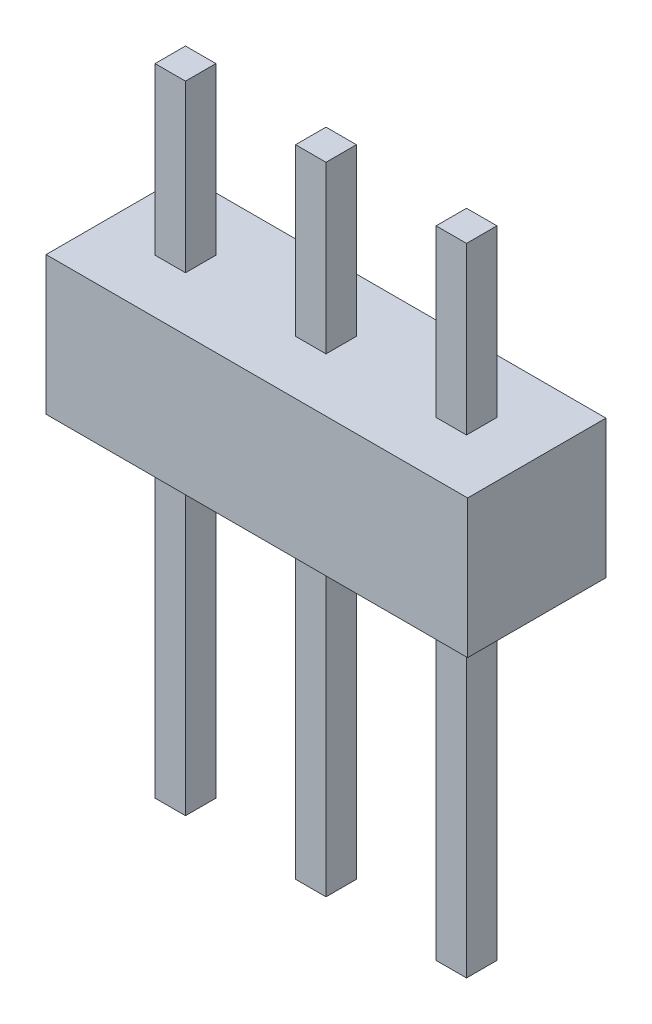
SolidWorks part; units mm, degrees
ref_plane "Front Plane" through (0, 0, 0) normal (0, 0, 1) x (1, 0, 0)
ref_plane "Top Plane" through (0, 0, 0) normal (0, 1, 0) x (1, 0, 0)
ref_plane "Right Plane" through (0, 0, 0) normal (1, 0, 0) x (0, 0, -1)
sketch "Sketch1" plane through (0, 0, 0) normal (0, 0, 1) x (1, 0, 0)
  line L1 (0, 0) -> (7.62, 0)
  line L2 (0, 0) -> (0, 2.5)
  line L3 (0, 2.5) -> (7.62, 2.5)
  line L4 (7.62, 0) -> (7.62, 2.5)
  dimension "D1" = 2.5
  dimension "D2" = 7.62
extrude "Boss-Extrude1" add sketch "Sketch1" along normal mid plane 2.5
sketch "Sketch2" plane through (0, 0, 0) normal (0, -1, 0) x (1, 0, 0)
  line L0 (0, 0) -> (7.62, 0) construction
  line L1 (7.62, 1.25) -> (7.62, -1.25) construction
  line L2 (3.535, -0.275) -> (4.085, -0.275)
  line L3 (0.995, -0.275) -> (1.545, -0.275)
  line L4 (0.995, -0.275) -> (0.995, 0.275)
  line L5 (0.995, 0.275) -> (1.545, 0.275)
  line L6 (1.545, -0.275) -> (1.545, 0.275)
  line L7 (0.995, -0.275) -> (1.545, 0.275) construction
  line L8 (0.995, 0.275) -> (1.545, -0.275) construction
  line L9 (3.535, -0.275) -> (3.535, 0.275)
  line L10 (3.535, 0.275) -> (4.085, 0.275)
  line L11 (4.085, -0.275) -> (4.085, 0.275)
  line L12 (3.535, -0.275) -> (4.085, 0.275) construction
  line L13 (3.535, 0.275) -> (4.085, -0.275) construction
  line L14 (1.27, 0) -> (3.81, 0) construction
  line L15 (6.075, -0.275) -> (6.625, -0.275)
  line L16 (6.075, -0.275) -> (6.075, 0.275)
  line L17 (6.075, 0.275) -> (6.625, 0.275)
  line L18 (6.625, -0.275) -> (6.625, 0.275)
  line L19 (6.075, -0.275) -> (6.625, 0.275) construction
  line L20 (6.075, 0.275) -> (6.625, -0.275) construction
  point P5 (1.27, 0)
  point P12 (3.81, 0)
  point P18 (6.35, 0)
  dimension "D1" = 0.55
  dimension "D3" = 1.27
  dimension "D4" = 2.54
  dimension "D2" = 3
extrude "Boss-Extrude2" add sketch "Sketch2" along normal blind 6 separate body
ref_axis "Axis1" through (1.27, 0, 0) along (0, -1, 0)
ref_axis "Axis2" through (6.35, 0, 0) along (0, -1, 0)
extrude "Boss-Extrude3" add sketch "Sketch2<2>" against normal blind 5.5 separate body
sketch "Sketch2<2>" plane through (0, 0, 0) normal (0, -1, 0) x (1, 0, 0) same geometry as "Sketch2"
